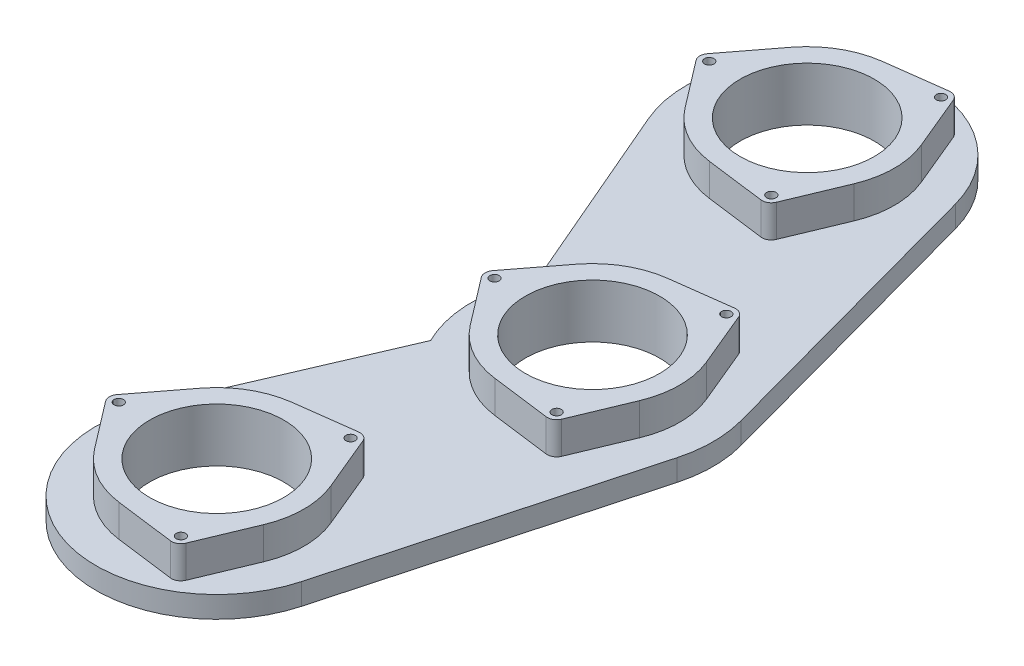
SolidWorks part; units mm, degrees
ref_plane "Alzado" through (0, 0, 0) normal (0, 0, 1) x (1, 0, 0)
ref_plane "Planta" through (0, 0, 0) normal (0, 1, 0) x (1, 0, 0)
ref_plane "Vista lateral" through (0, 0, 0) normal (1, 0, 0) x (0, 0, -1)
sketch "Croquis5" plane through (0, 0, 0) normal (0, 1, 0) x (1, 0, 0)
  line L0 (0, 176.3184) -> (0, -176.3184) construction
  line L1 (-217.2635, 0) -> (217.2635, 0) construction
  line L2 (13.4144, 121.8403) -> (43.4144, 11.8403)
  line L3 (43.4144, -11.8403) -> (13.4144, -121.8403)
  line L6 (-71.3458, 92.237) -> (-40.3113, 20)
  line L7 (-71.3458, -92.237) -> (-40.3113, -20)
  circle A0 centre (0, 0) radius 45
  circle A1 centre (-30, 110) radius 45
  circle A2 centre (-30, -110) radius 45
  point P6 (0, 0)
  point P9 (0, 0)
  dimension "D1" = 90
  dimension "D2" = 220
  dimension "D3" = 30
  dimension "D4" = 20
sketch "Croquis1" plane through (0, 0, 0) normal (0, 1, 0) x (1, 0, 0)
  line L16 (-71.3458, 92.237) -> (-40.3113, 20) construction
  line L17 (-71.3458, -92.237) -> (-40.3113, -20) construction
  line L18 (43.4144, -11.8403) -> (13.4144, -121.8403) construction
  line L19 (13.4144, 121.8403) -> (43.4144, 11.8403) construction
  line L20 (-71.3458, 92.237) -> (-40.3113, 20)
  line L21 (-71.3458, -92.237) -> (-40.3113, -20)
  line L22 (43.4144, -11.8403) -> (13.4144, -121.8403)
  line L23 (13.4144, 121.8403) -> (43.4144, 11.8403)
  circle A10 centre (-30, -110) radius 45 construction
  circle A11 centre (0, 0) radius 45 construction
  circle A12 centre (-30, 110) radius 45 construction
  arc A13 (-71.3458, -92.237) -> (13.4144, -121.8403) centre (-30, -110) ccw
  arc A14 (-40.3113, 20) -> (-40.3113, -20) centre (0, 0) ccw
  arc A15 (13.4144, 121.8403) -> (-71.3458, 92.237) centre (-30, 110) ccw
  arc A16 (43.4144, -11.8403) -> (43.4144, 11.8403) centre (0, 0) ccw
extrude "Saliente-Extruir1" add sketch "Croquis1" along normal blind 8
sketch "Croquis6" plane through (0, 8, 0) normal (0, 1, 0) x (1, 0, 0)
  line L2 (0, 0) -> (-32.5, 0) construction
  line L22 (-39.2808, 2.1253) -> (-25.8219, 19.7352)
  line L23 (-39.2808, -2.1253) -> (-25.8219, -19.7352)
  line L24 (21.481, 32.9555) -> (30.0022, 12.4948)
  line L25 (17.7998, 35.0809) -> (-4.1802, 32.23)
  line L26 (17.7998, -35.0809) -> (-4.1802, -32.23)
  line L27 (21.481, -32.9555) -> (30.0022, -12.4948)
  line L28 (0, 0) -> (-25.8219, 19.7352) construction
  line L33 (-69.2808, -107.8747) -> (-55.8219, -90.2648)
  line L36 (-8.519, -142.9555) -> (0.0022, -122.4948)
  line L40 (-69.2808, -112.1253) -> (-55.8219, -129.7352)
  line L42 (-30, -110) -> (-62.5, -110) construction
  line L45 (-30, -110) -> (-55.8219, -90.2648) construction
  line L46 (-12.2002, -74.9191) -> (-34.1802, -77.77)
  line L47 (-12.2002, -145.0809) -> (-34.1802, -142.23)
  line L48 (-8.519, -77.0445) -> (0.0022, -97.5052)
  line L49 (-69.2808, 107.8747) -> (-55.8219, 90.2648)
  line L50 (-12.2002, 145.0809) -> (-34.1802, 142.23)
  line L51 (-30, 110) -> (-55.8219, 129.7352) construction
  line L52 (-8.519, 142.9555) -> (0.0022, 122.4948)
  line L53 (-30, 110) -> (-62.5, 110) construction
  line L54 (-12.2002, 74.9191) -> (-34.1802, 77.77)
  line L55 (-69.2808, 112.1253) -> (-55.8219, 129.7352)
  line L56 (-8.519, 77.0445) -> (0.0022, 97.5052)
  arc A25 (-25.8219, -19.7352) -> (-4.1802, -32.23) centre (0, 0) ccw
  arc A26 (-39.2808, 2.1253) -> (-39.2808, -2.1253) centre (-36.5, 0) ccw
  arc A27 (21.481, 32.9555) -> (17.7998, 35.0809) centre (18.25, 31.6099) ccw
  arc A28 (17.7998, -35.0809) -> (21.481, -32.9555) centre (18.25, -31.6099) ccw
  arc A29 (-4.1802, 32.23) -> (-25.8219, 19.7352) centre (0, 0) ccw
  arc A30 (30.0022, -12.4948) -> (30.0022, 12.4948) centre (0, 0) ccw
  arc A43 (-55.8219, -129.7352) -> (-34.1802, -142.23) centre (-30, -110) ccw
  arc A44 (-8.519, -77.0445) -> (-12.2002, -74.9191) centre (-11.75, -78.3901) ccw
  arc A45 (-34.1802, -77.77) -> (-55.8219, -90.2648) centre (-30, -110) ccw
  arc A46 (-69.2808, -107.8747) -> (-69.2808, -112.1253) centre (-66.5, -110) ccw
  arc A47 (0.0022, -122.4948) -> (0.0022, -97.5052) centre (-30, -110) ccw
  arc A48 (-12.2002, -145.0809) -> (-8.519, -142.9555) centre (-11.75, -141.6099) ccw
  arc A49 (-34.1802, 142.23) -> (-55.8219, 129.7352) centre (-30, 110) ccw
  arc A50 (-12.2002, 74.9191) -> (-8.519, 77.0445) centre (-11.75, 78.3901) ccw
  arc A51 (-69.2808, 112.1253) -> (-69.2808, 107.8747) centre (-66.5, 110) ccw
  arc A52 (-55.8219, 90.2648) -> (-34.1802, 77.77) centre (-30, 110) ccw
  arc A53 (-8.519, 142.9555) -> (-12.2002, 145.0809) centre (-11.75, 141.6099) ccw
  arc A54 (0.0022, 97.5052) -> (0.0022, 122.4948) centre (-30, 110) ccw
  dimension "D1" = 32.5
  dimension "D2" = 7
  dimension "D3" = 4
  dimension "D5" = 32.5
  dimension "D6" = 7
  dimension "D4" = 3
  dimension "D9" = 32.5
  dimension "D10" = 7
  dimension "D7" = 32.5
  dimension "D8" = 4
  dimension "D11" = 32.5
  dimension "D12" = 4
  dimension "D13" = 32.5
extrude "Saliente-Extruir2" add sketch "Croquis6" along normal blind 12
sketch "Croquis7" plane through (0, 8, 0) normal (0, 1, 0) x (1, 0, 0)
  circle A26 centre (0, 0) radius 25
  circle A27 centre (-30, 110) radius 25
  circle A28 centre (-30, -110) radius 25
  circle A29 centre (-36.5, 0) radius 1.75
  circle A30 centre (18.25, -31.6099) radius 1.75
  circle A31 centre (18.25, 31.6099) radius 1.75
  circle A32 centre (-11.75, 141.6099) radius 1.75
  circle A33 centre (-66.5, 110) radius 1.75
  circle A34 centre (-11.75, 78.3901) radius 1.75
  circle A35 centre (-66.5, -110) radius 1.75
  circle A36 centre (-11.75, -141.6099) radius 1.75
  circle A37 centre (-11.75, -78.3901) radius 1.75
  dimension "D1" = 50
  dimension "D2" = 3.5
extrude "Cortar-Extruir3" cut sketch "Croquis7" against normal through all both and the other way through all
